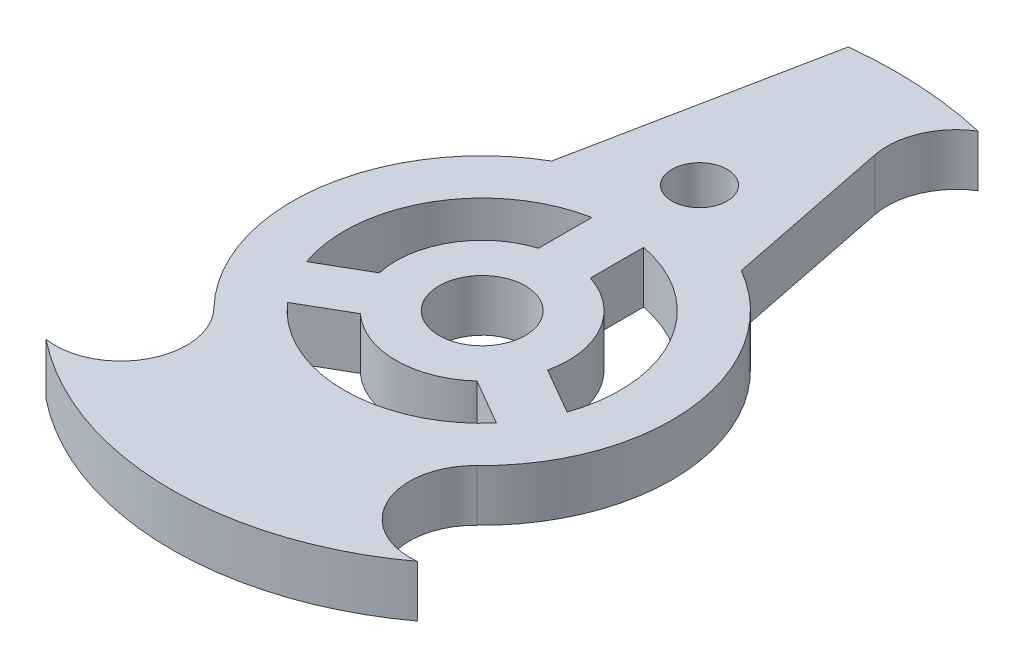
SolidWorks part; units mm, degrees
material "AISI Type A2 Tool Steel"
ref_plane "Front Plane" through (0, 0, 0) normal (0, 0, 1) x (1, 0, 0)
ref_plane "Top Plane" through (0, 0, 0) normal (0, 1, 0) x (1, 0, 0)
ref_plane "Right Plane" through (0, 0, 0) normal (1, 0, 0) x (0, 0, -1)
other "Center of Mass"
other "Bounding Box"
ref_plane "Default Plane" through (-8.9266, -12.7485, 0) normal (-0.1736, 0.9848, 0) x (0.9848, 0.1736, 0)
sketch "Sketch1" plane through (0, 0, 0) normal (0, 1, 0) x (1, 0, 0)
  circle A0 centre (0, 0) radius 7.9375
  circle A1 centre (0, 0) radius 34.925
  circle A2 centre (0, 0) radius 76.2 construction
  dimension "D1" = 15.875
  dimension "D2" = 152.4
  dimension "D3" = 69.85
extrude "Boss-Extrude1" add sketch "Sketch1" along normal mid plane 9.525
sketch "Sketch2" plane through (0, 4.7625, 0) normal (0, 1, 0) x (1, 0, 0)
  line L0 (-17.4625, 30.2459) -> (-8.3548, 75.7406)
  line L1 (17.4625, 30.2459) -> (11.3002, 61.0281)
  line L2 (-8.3548, 75.7406) -> (17.0031, 74.2788) construction
  line L3 (0, 0) -> (0, 76.2) construction
  line L4 (0, 0) -> (17.0031, 74.2788) construction
  line L5 (17.0031, 74.2788) -> (-74.2788, 17.0031) construction
  line L6 (-17.4625, 30.2459) -> (0, 30.2459) construction
  line L7 (0, 30.2459) -> (17.4625, 30.2459) construction
  line L8 (-8.3548, 75.7406) -> (0, 117.4747) construction
  line L9 (0, 117.4747) -> (11.3002, 61.0281) construction
  circle A0 centre (0, 0) radius 34.925 construction
  circle A1 centre (0, 0) radius 76.2 construction
  arc A2 (-8.3548, 75.7406) -> (17.0031, 74.2788) centre (0, 0) cw
  arc A3 (11.3002, 61.0281) -> (17.0031, 74.2788) centre (23.7531, 63.5211) cw
  arc A4 (17.4625, 30.2459) -> (-17.4625, 30.2459) centre (0, 0) ccw
  circle A5 centre (0, 0) radius 34.925 construction
  dimension "D1" = 45
  dimension "D3" = 12.7
  dimension "D2" = 25.4
  dimension "D4" = 34.925
extrude "Boss-Extrude2" add sketch "Sketch2" against normal up to surface (9.525 mm away) up to face at (0, -4.7625, 34.925)
sketch "Sketch3" plane through (0, 4.7625, 0) normal (0, 1, 0) x (1, 0, 0)
  line L0 (-35.5767, -44.7261) -> (0, 0) construction
  line L1 (0, 0) -> (33.9941, -45.9404) construction
  line L2 (0, 0) -> (0, -76.2) construction
  line L3 (0, 0) -> (-1.3299, -76.1884) construction
  line L4 (-35.5767, -44.7261) -> (49.9863, -57.5135) construction
  arc A0 (-35.5767, -44.7261) -> (33.9941, -45.9404) centre (0, 0) ccw
  arc A1 (-35.5767, -44.7261) -> (-25.0811, -24.3042) centre (-33.7852, -32.7388) ccw
  circle A2 centre (0, 0) radius 34.925 construction
  arc A3 (33.9941, -45.9404) -> (24.2176, -25.1648) centre (32.6221, -33.8979) cw
  arc A4 (-25.0811, -24.3042) -> (24.2176, -25.1648) centre (0, 0) ccw
  circle A5 centre (0, 0) radius 76.2 construction
  point P6 (-0.9974, -57.1413)
  dimension "D1" = 57.15
  dimension "D2" = 75
  dimension "D3" = 1
  dimension "D4" = 60
extrude "Boss-Extrude3" add sketch "Sketch3" against normal up to surface (9.525 mm away) up to face at (3.5891, -4.7625, -41.6642)
sketch "Sketch4" plane through (0, 4.7625, 0) normal (0, 1, 0) x (1, 0, 0)
  line L0 (15.4962, -3.4474) -> (23.9882, -8.3503)
  line L1 (4.7625, 15.1438) -> (4.7625, 24.9495)
  line L2 (0, 0) -> (30.2459, -17.4625) construction
  line L3 (0, 0) -> (0, 34.925) construction
  line L4 (4.7625, 24.9495) -> (0, 24.9495) construction
  line L5 (23.9882, -8.3503) -> (21.6069, -12.4748) construction
  arc A0 (4.7625, 15.1438) -> (15.4962, -3.4474) centre (0, 0) cw
  arc A1 (4.7625, 24.9495) -> (23.9882, -8.3503) centre (0, 0) cw
  circle A2 centre (0, 0) radius 34.925 construction
  dimension "D2" = 9.525
  dimension "D3" = 15.875
  dimension "D1" = 4.7625
  dimension "D4" = 120
extrude "Cut-Extrude1" cut sketch "Sketch4" against normal through all
pattern_circular "CirPattern1" count 3 over 360 about axis through (0, 4.7625, 0) along (0, -1, 0) of "Cut-Extrude1" reverse direction yes
sketch "Sketch5" plane through (0, 4.7625, 0) normal (0, 1, 0) x (1, 0, 0)
  line L0 (0, 0) -> (0, 76.2) construction
  circle A0 centre (0, 40.005) radius 5.08
  arc A1 (17.4625, 30.2459) -> (-17.4625, 30.2459) centre (0, 0) ccw construction
  dimension "D1" = 10.16
extrude "Cut-Extrude2" cut sketch "Sketch5" against normal through all
